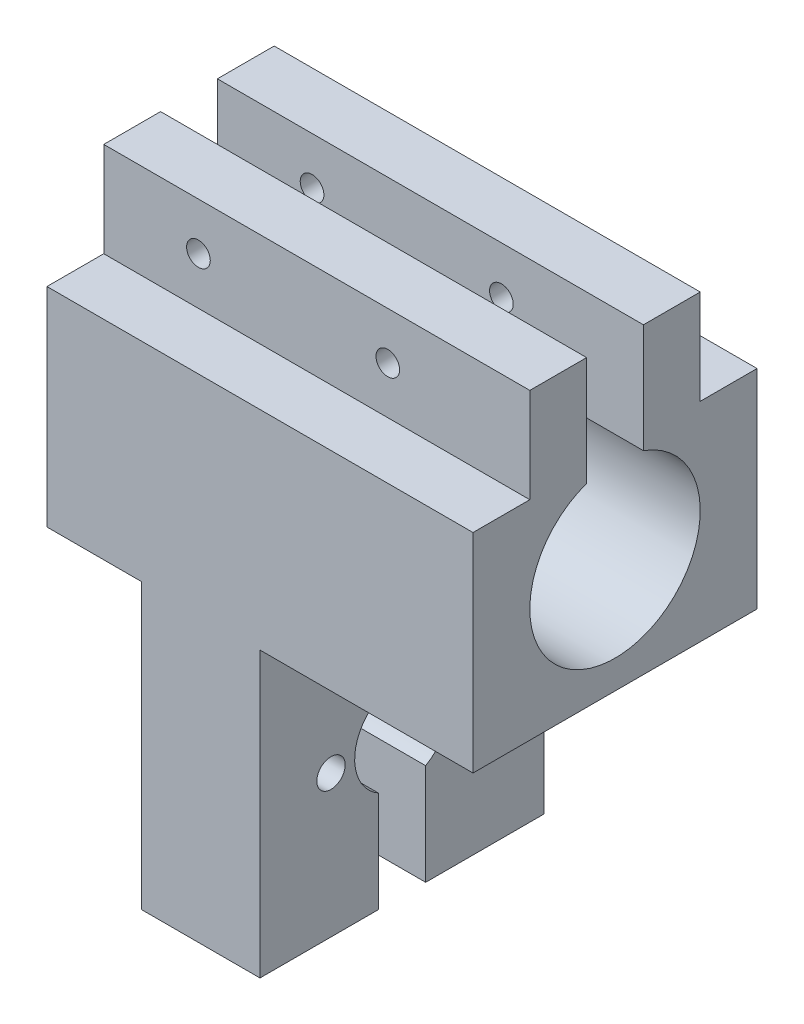
SolidWorks part; units mm, degrees
ref_plane "Front Plane" through (0, 0, 0) normal (0, 0, 1) x (1, 0, 0)
ref_plane "Top Plane" through (0, 0, 0) normal (0, 1, 0) x (1, 0, 0)
ref_plane "Right Plane" through (0, 0, 0) normal (1, 0, 0) x (0, 0, -1)
sketch "Sketch1" plane through (0, 0, 0) normal (1, 0, 0) x (0, 0, -1)
  line L0 (-24, 50) -> (-24, 40)
  line L2 (0, 0) -> (0, 40)
  line L3 (-6, 50) -> (-12, 50)
  line L4 (-30, 0) -> (-30, 40)
  line L5 (-18, 38.4853) -> (-18, 50)
  line L6 (-12, 50) -> (-12, 38.4853)
  line L7 (-18, 50) -> (-24, 50)
  line L8 (-24, 40) -> (-30, 40)
  line L9 (-6, 50) -> (-6, 40)
  line L10 (-6, 40) -> (0, 40)
  line L11 (-30, 0) -> (-30, -12)
  line L12 (-30, -12) -> (0, -12)
  line L13 (0, -12) -> (0, 0)
  arc A0 (-18, 38.4853) -> (-12, 38.4853) centre (-15, 30) ccw
  circle A1 centre (-15, 3) radius 5
  point P16 (-3, 40)
  dimension "D3" = 18
  dimension "D1" = 10
  dimension "D2" = 30
  dimension "D4" = 20
  dimension "D5" = 6
  dimension "D6" = 3
  dimension "D7" = 15
  dimension "D8" = 27
  dimension "D9" = 15
  dimension "D10" = 10
  dimension "D11" = 6
  dimension "D12" = 6
  dimension "D13" = 10
  dimension "D14" = 52
  dimension "D15" = 40
  dimension "D16" = 30
extrude "Boss-Extrude1" add sketch "Sketch1" along normal mid plane 45
sketch "Sketch3" plane through (0, 0, 0) normal (0, 0, -1) x (-1, 0, 0)
  line L0 (-22.5, -12) -> (22.5, -12) construction
  line L6 (22.5, 40) -> (22.5, -12) construction
  line L7 (22.5, 18) -> (12.5, 18)
  line L8 (22.5, 18) -> (22.5, -12)
  line L9 (22.5, -12) -> (12.5, -12)
  line L10 (12.5, 18) -> (12.5, -12)
  dimension "D1" = 10
  dimension "D2" = 30
extrude "Cut-Extrude1" cut sketch "Sketch3" against normal blind 45 contours L7 L10 L9 L8
sketch "Sketch4" plane through (-12.5, 0, 0) normal (-1, 0, 0) x (0, 0, 1)
  line L0 (20, 3) -> (0, 3) construction
  line L1 (0, 18) -> (0, -12) construction
  line L2 (0, 3) -> (30, 3) construction
  line L3 (30, 18) -> (30, -12) construction
  circle A0 centre (15, 3) radius 5 construction
  circle A1 centre (7.5, 3) radius 1.5
  circle A2 centre (22.5, 3) radius 1.5
  point P9 (22.5, 3)
  point P10 (7.5, 3)
  dimension "D1" = 15
  dimension "D2" = 7.5
extrude "Cut-Extrude2" cut sketch "Sketch4" against normal blind 45 contours A2
extrude "Cut-Extrude3" cut sketch "Sketch4<3>" against normal blind 45 contours A1
sketch "Sketch4<3>" plane through (-12.5, 0, 0) normal (-1, 0, 0) x (0, 0, 1) same geometry as "Sketch4"
sketch "Sketch6" plane through (0, 0, 0) normal (0, 0, -1) x (-1, 0, 0)
  line L0 (-22.5, -12) -> (12.5, -12) construction
  line L1 (0, -12) -> (-10, -12)
  line L2 (0, -12) -> (0, 18)
  line L3 (0, 18) -> (-10, 18)
  line L4 (-10, -12) -> (-10, 18)
  dimension "D1" = 12.5
  dimension "D2" = 10
  dimension "D3" = 30
extrude "Cut-Extrude4" cut sketch "Sketch6" against normal blind 45
sketch "Sketch7" plane through (0, 0, 0) normal (0, 0, -1) x (-1, 0, 0)
  line L1 (-22.5, -12) -> (-10, -12)
  line L2 (-22.5, -12) -> (-22.5, 18)
  line L3 (-22.5, 18) -> (-10, 18)
  line L4 (-10, -12) -> (-10, 18)
extrude "Cut-Extrude5" cut sketch "Sketch7" against normal blind 45
sketch "Sketch8" plane through (0, 0, 0) normal (1, 0, 0) x (0, 0, -1)
  line L0 (-30, -12) -> (0, -12) construction
  line L1 (-17.5, -12) -> (-12.5, -12)
  line L2 (-17.5, -12) -> (-17.5, -1.3301)
  line L3 (-17.5, -1.3301) -> (-12.5, -1.3301)
  line L4 (-12.5, -12) -> (-12.5, -1.3301)
  circle A0 centre (-15, 3) radius 5 construction
  point P8 (0, 0)
  point P12 (-7.7801, -15.0816)
  dimension "D1" = 5
  dimension "D2" = 2.5
extrude "Cut-Extrude6" cut sketch "Sketch8" against normal blind 45
sketch "Sketch9" plane through (0, 0, 6) normal (0, 0, -1) x (-1, 0, 0)
  line L0 (22.5, 50) -> (22.5, 40) construction
  line L1 (-22.5, 50) -> (22.5, 50) construction
  circle A0 centre (12.5, 45) radius 1.25
  circle A1 centre (-7.5, 45) radius 1.25
  dimension "D1" = 2.5
  dimension "D2" = 2.5
  dimension "D3" = 20
  dimension "D4" = 10
  dimension "D5" = 5
  dimension "D6" = 5
extrude "Cut-Extrude7" cut sketch "Sketch9" against normal blind 150
